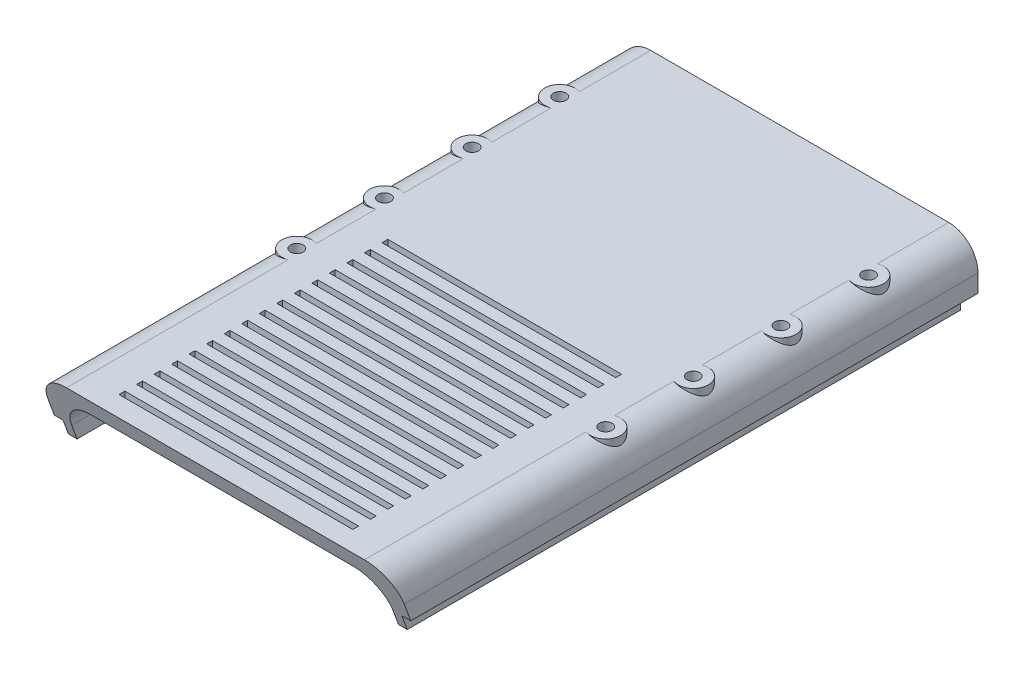
SolidWorks part; units mm, degrees
ref_plane "Alzado" through (0, 0, 0) normal (0, 0, 1) x (1, 0, 0)
ref_plane "Planta" through (0, 0, 0) normal (0, 1, 0) x (1, 0, 0)
ref_plane "Vista lateral" through (0, 0, 0) normal (1, 0, 0) x (0, 0, -1)
sketch "Croquis1" plane through (0, 0, 0) normal (0, 0, 1) x (1, 0, 0)
  line L0 (-45, -46) -> (-45, -52) construction
  line L1 (-45, 46) -> (45, 46)
  line L2 (-55, 36) -> (-55, -36) construction
  line L3 (-45, -46) -> (45, -46) construction
  line L4 (55, 31) -> (55, -36) construction
  line L5 (-55, 46) -> (55, -46) construction
  line L6 (-55, -46) -> (55, 46) construction
  line L7 (51, -52) -> (-51, -52) construction
  line L8 (61, -42) -> (61, 36) construction
  line L9 (51, 52) -> (-51, 52)
  line L10 (-61, -42) -> (-61, 36) construction
  line L11 (61, -52) -> (-61, 52) construction
  line L12 (61, 52) -> (-61, -52) construction
  line L13 (-55, -36) -> (-61, -36) construction
  line L14 (-55, 36) -> (55, 36)
  line L15 (0, 52) -> (0, 36) construction
  line L16 (-61, 36) -> (-58, 36)
  line L17 (58, 36) -> (61, 36)
  line L18 (61, 36) -> (61, 42)
  line L19 (-61, 36) -> (-61, 42)
  line L24 (58, 36) -> (58, 31)
  line L25 (58, 31) -> (55, 31)
  line L26 (55, 36) -> (55, 31)
  line L27 (55, 36) -> (58, 36) construction
  line L28 (-55, 36) -> (-55, 31)
  line L29 (-58, 31) -> (-55, 31)
  line L30 (-58, 36) -> (-58, 31)
  line L31 (-58, 36) -> (-55, 36) construction
  arc A0 (-45, 46) -> (-55, 36) centre (-45, 36) ccw
  arc A1 (45, 46) -> (55, 36) centre (45, 36) cw
  arc A2 (45, -46) -> (55, -36) centre (45, -36) ccw construction
  arc A3 (-55, -36) -> (-45, -46) centre (-45, -36) ccw construction
  arc A4 (51, -52) -> (61, -42) centre (51, -42) ccw construction
  arc A5 (61, 42) -> (51, 52) centre (51, 42) ccw
  arc A6 (-51, -52) -> (-61, -42) centre (-51, -42) cw construction
  arc A7 (-51, 52) -> (-61, 42) centre (-51, 42) ccw
  point P0 (0, 0)
  point P18 (0, 0)
  dimension "D1" = 10
  dimension "D4" = 10
  dimension "D2" = 110
  dimension "D3" = 92
  dimension "D5" = 6
  dimension "D6" = 5
  dimension "D7" = 3
extrude "Saliente-Extruir1" add sketch "Croquis1" along normal blind 3 contours A1 L1 A0 L14 region at (0, 40.8877, 0)
extrude "Saliente-Extruir2" add sketch "Croquis1<3>" along normal blind 200 contours L9 A7 L19 L16 L30 L29 L28 A0 L1 A1 L26 L25 L24 L17 L18 A5 region at (0, 47.0924, 0)
sketch "Croquis1<3>" plane through (0, 0, 0) normal (0, 0, 1) x (1, 0, 0) same geometry as "Croquis1"
sketch "Croquis4" plane through (61, 0, 0) normal (1, 0, 0) x (0, 0, -1)
  line L0 (-200, 52) -> (-200, 31)
  line L1 (-200, 31) -> (-192.3566, 31)
  line L3 (-192.3566, 31) -> (-200, 52)
  line L5 (-200, 31) -> (0, 31) construction
  dimension "D1" = 70
extrude "Cortar-Extruir3" cut sketch "Croquis4" against normal through all
sketch "Croquis6" plane through (0, 52, 0) normal (0, 1, 0) x (1, 0, 0)
  line L0 (0, 0) -> (0, -192) construction
  line L1 (-40, -193) -> (40, -193)
  line L2 (-40, -193) -> (-40, -191)
  line L3 (-40, -191) -> (40, -191)
  line L4 (40, -193) -> (40, -191)
  line L5 (-40, -193) -> (40, -191) construction
  line L6 (-40, -191) -> (40, -193) construction
  line L7 (-40, -187) -> (40, -187)
  line L8 (0, -192) -> (0, -200) construction
  line L9 (51, -200) -> (-51, -200) construction
  line L10 (40, -187) -> (40, -185)
  line L11 (-40, -185) -> (40, -185)
  line L12 (-40, -187) -> (-40, -185)
  line L13 (-40, -181) -> (40, -181)
  line L14 (40, -181) -> (40, -179)
  line L15 (-40, -179) -> (40, -179)
  line L16 (-40, -181) -> (-40, -179)
  line L17 (-40, -175) -> (40, -175)
  line L18 (40, -175) -> (40, -173)
  line L19 (-40, -173) -> (40, -173)
  line L20 (-40, -175) -> (-40, -173)
  line L21 (-40, -169) -> (40, -169)
  line L22 (40, -169) -> (40, -167)
  line L23 (-40, -167) -> (40, -167)
  line L24 (-40, -169) -> (-40, -167)
  line L25 (-40, -163) -> (40, -163)
  line L26 (40, -163) -> (40, -161)
  line L27 (-40, -161) -> (40, -161)
  line L28 (-40, -163) -> (-40, -161)
  line L29 (-40, -157) -> (40, -157)
  line L30 (40, -157) -> (40, -155)
  line L31 (-40, -155) -> (40, -155)
  line L32 (-40, -157) -> (-40, -155)
  line L33 (-40, -151) -> (40, -151)
  line L34 (40, -151) -> (40, -149)
  line L35 (-40, -149) -> (40, -149)
  line L36 (-40, -151) -> (-40, -149)
  line L37 (-40, -145) -> (40, -145)
  line L38 (40, -145) -> (40, -143)
  line L39 (-40, -143) -> (40, -143)
  line L40 (-40, -145) -> (-40, -143)
  line L41 (-40, -139) -> (40, -139)
  line L42 (40, -139) -> (40, -137)
  line L43 (-40, -137) -> (40, -137)
  line L44 (-40, -139) -> (-40, -137)
  line L45 (-40, -133) -> (40, -133)
  line L46 (40, -133) -> (40, -131)
  line L47 (-40, -131) -> (40, -131)
  line L48 (-40, -133) -> (-40, -131)
  line L49 (-40, -127) -> (40, -127)
  line L50 (40, -127) -> (40, -125)
  line L51 (-40, -125) -> (40, -125)
  line L52 (-40, -127) -> (-40, -125)
  line L53 (-40, -121) -> (40, -121)
  line L54 (40, -121) -> (40, -119)
  line L55 (-40, -119) -> (40, -119)
  line L56 (-40, -121) -> (-40, -119)
  line L57 (-40, -115) -> (40, -115)
  line L58 (40, -115) -> (40, -113)
  line L59 (-40, -113) -> (40, -113)
  line L60 (-40, -115) -> (-40, -113)
  line L61 (-40, -109) -> (40, -109)
  line L62 (40, -109) -> (40, -107)
  line L63 (-40, -107) -> (40, -107)
  line L64 (-40, -109) -> (-40, -107)
  line L65 (-40, -103) -> (40, -103)
  line L66 (40, -103) -> (40, -101)
  line L67 (-40, -101) -> (40, -101)
  line L68 (-40, -103) -> (-40, -101)
  line L69 (-40, -193) -> (-40, -187) construction
  point P0 (0, -192)
  dimension "D1" = 2
  dimension "D2" = 80
  dimension "D3" = 8
  dimension "D5" = 6
  dimension "D4" = 16
extrude "Cortar-Extruir5" cut sketch "Croquis6" against normal up to next
sketch "Croquis7" plane through (0, 36, 0) normal (0, -1, 0) x (1, 0, 0)
  line L0 (0, 0) -> (0, 3) construction
  line L1 (-45, 3) -> (45, 3) construction
  line L2 (-58, 0) -> (-58, 3)
  line L3 (58, 0) -> (55, 0)
  line L4 (58, 0) -> (58, 3)
  line L5 (58, 3) -> (55, 3)
  line L6 (55, 0) -> (55, 3)
  line L7 (-58, 0) -> (-55, 0)
  line L8 (-55, 0) -> (-55, 3)
  line L9 (-58, 3) -> (-55, 3)
extrude "Cortar-Extruir6" cut sketch "Croquis7" along normal up to surface (5 mm away) up to face at (56.5, 31, 96.1783)
sketch "Croquis8" plane through (0, 52, 0) normal (0, 1, 0) x (1, 0, 0)
  line L0 (0, 0) -> (0, -200) construction
  line L1 (51, -200) -> (-51, -200) construction
  circle A0 centre (-52.85, -119.3) radius 2.15
  circle A1 centre (-52.85, -119.3) radius 5.15
  circle A2 centre (-52.85, -89.3) radius 2.15
  circle A3 centre (-52.85, -89.3) radius 5.0926
  circle A4 centre (-52.85, -59.3) radius 2.1582
  circle A5 centre (-52.85, -59.3) radius 5.15
  circle A6 centre (-52.85, -29.3) radius 2.15
  circle A7 centre (-52.85, -29.3) radius 5.15
  circle A8 centre (52.85, -119.3) radius 2.15
  circle A9 centre (52.85, -119.3) radius 5.15
  circle A10 centre (52.85, -89.3) radius 2.15
  circle A11 centre (52.85, -89.3) radius 5.15
  circle A12 centre (52.85, -59.3) radius 2.1566
  circle A13 centre (52.85, -59.3) radius 5.15
  circle A14 centre (52.85, -29.3) radius 2.15
  circle A15 centre (52.85, -29.3) radius 5.15
  point P38 (0, 0)
ref_plane "Plano1" through (-55, 31, 24.6203) normal (-0.9087, 0, 0.4175) x (0.4175, 0, 0.9087)
extrude "Saliente-Extruir3" add sketch "Croquis8" against normal up to vertex up to point (58, 31, 192.3566)
extrude "Cortar-Extruir7" cut sketch "Croquis8<2>" against normal up to next contours A6 | A4 | A2 | A0 | A8 | A10 | A12 | A14 region at (-52.85, 52, 119.3) region at (-52.85, 52, 89.3) region at (-52.85, 52, 59.3) region at (-52.85, 52, 29.3) region at (52.85, 52, 119.3) region at (52.85, 52, 89.3) region at (52.85, 52, 59.3) region at (52.85, 52, 29.3)
sketch "Croquis8<2>" plane through (0, 52, 0) normal (0, 1, 0) x (1, 0, 0) same geometry as "Croquis8"
equation "\"D4@Croquis1\"=\"D1@Croquis1\""
